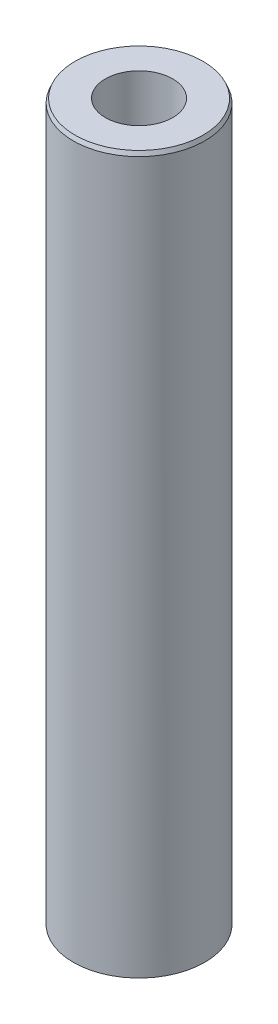
SolidWorks part; units mm, degrees
ref_plane "Front Plane" through (0, 0, 0) normal (0, 0, 1) x (1, 0, 0)
ref_plane "Top Plane" through (0, 0, 0) normal (0, 1, 0) x (1, 0, 0)
ref_plane "Right Plane" through (0, 0, 0) normal (1, 0, 0) x (0, 0, -1)
sketch "Sketch1" plane through (0, 0, 0) normal (0, 1, 0) x (1, 0, 0)
  circle A0 centre (0, 0) radius 55
  dimension "SHAFT_OD" = 110
extrude "Boss-Extrude1" add sketch "Sketch1" along normal blind 600
sketch "Sketch2" plane through (0, 0, 0) normal (0, 1, 0) x (1, 0, 0)
  circle A0 centre (0, 0) radius 28.1391
  dimension "BORE_D" = 56.2782
extrude "Cut-Extrude1" cut sketch "Sketch2" along normal through all
chamfer "Chamfer1" distance 3.4384 angle 22.728 2 edges at (0, 600, 55) (0, 0, 55) first distance on face at (0, 600, 55) first distance on face at (0, 0, 28.1391)
